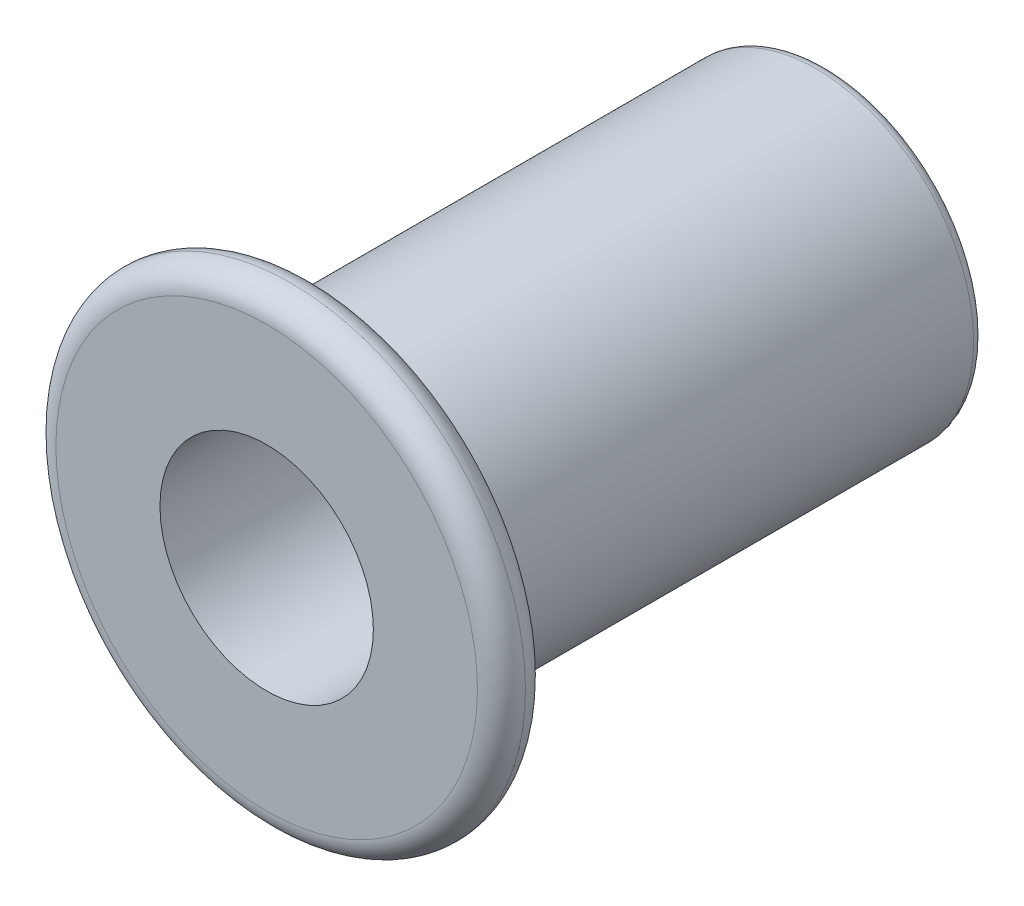
SolidWorks part; units mm, degrees
material "黄铜"
ref_plane "前视基准面" through (0, 0, 0) normal (0, 0, 1) x (1, 0, 0)
ref_plane "上视基准面" through (0, 0, 0) normal (0, 1, 0) x (1, 0, 0)
ref_plane "右视基准面" through (0, 0, 0) normal (1, 0, 0) x (0, 0, -1)
sketch "草图1" plane through (0, 0, 0) normal (0, 0, 1) x (1, 0, 0)
  circle A0 centre (0, 0) radius 2
  circle A1 centre (0, 0) radius 2.95
  dimension "内径" = 4
  dimension "外径" = 5.9
extrude "凸台-拉伸1" add sketch "草图1" against normal blind 9.6
sketch "草图2" plane through (0, 0, 0) normal (0, 0, 1) x (1, 0, 0)
  circle A0 centre (0, 0) radius 2
  circle A1 centre (0, 0) radius 4.4
  circle A2 centre (0, 0) radius 2 construction
  dimension "D1" = 8.8
extrude "凸台-拉伸2" add sketch "草图2" along normal blind 0.9
fillet "圆角1" radius 0.45 2 edges at (4.4, 0, 0) (4.4, 0, 0.9)
fillet "圆角2" radius 0.2 2 edges at (2, 0, -9.6) (2.95, 0, -9.6)
other "冻结***"
